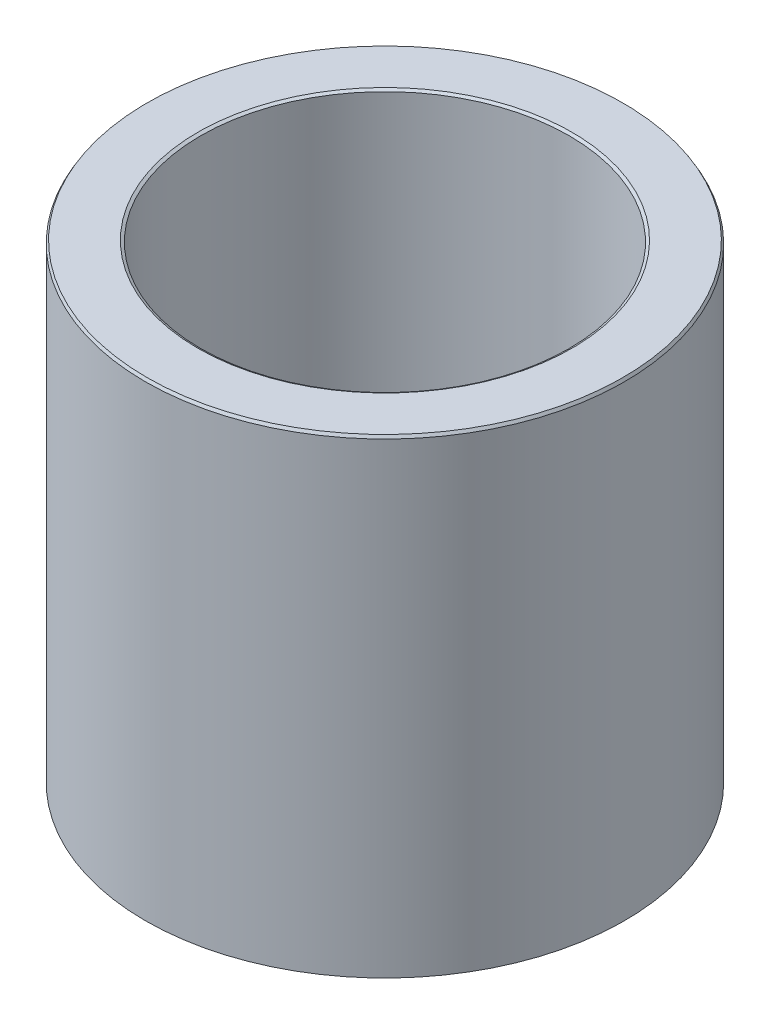
SolidWorks part; units mm, degrees
ref_plane "Front Plane" through (0, 0, 0) normal (0, 0, 1) x (1, 0, 0)
ref_plane "Top Plane" through (0, 0, 0) normal (0, 1, 0) x (1, 0, 0)
ref_plane "Right Plane" through (0, 0, 0) normal (1, 0, 0) x (0, 0, -1)
sketch "Sketch1" plane through (0, 0, 0) normal (0, 1, 0) x (1, 0, 0)
  circle A0 centre (0, 0) radius 55
  dimension "SLEEVE_OD" = 110
extrude "Boss-Extrude1" add sketch "Sketch1" along normal blind 108.2017
sketch "Sketch2" plane through (0, 0, 0) normal (0, 1, 0) x (1, 0, 0)
  circle A0 centre (0, 0) radius 42.3142
  dimension "BORE_D" = 84.6285
extrude "Cut-Extrude1" cut sketch "Sketch2" along normal through all
chamfer "Chamfer1" distance 0.6471 angle 30 4 edges at (0, 108.2017, 42.3142) (0, 0, 42.3142) (0, 0, 55) (0, 108.2017, 55) first distance on face at (0, 108.2017, 42.3142) first distance on face at (0, 0, 42.3142) first distance on face at (0, 108.2017, 55)
